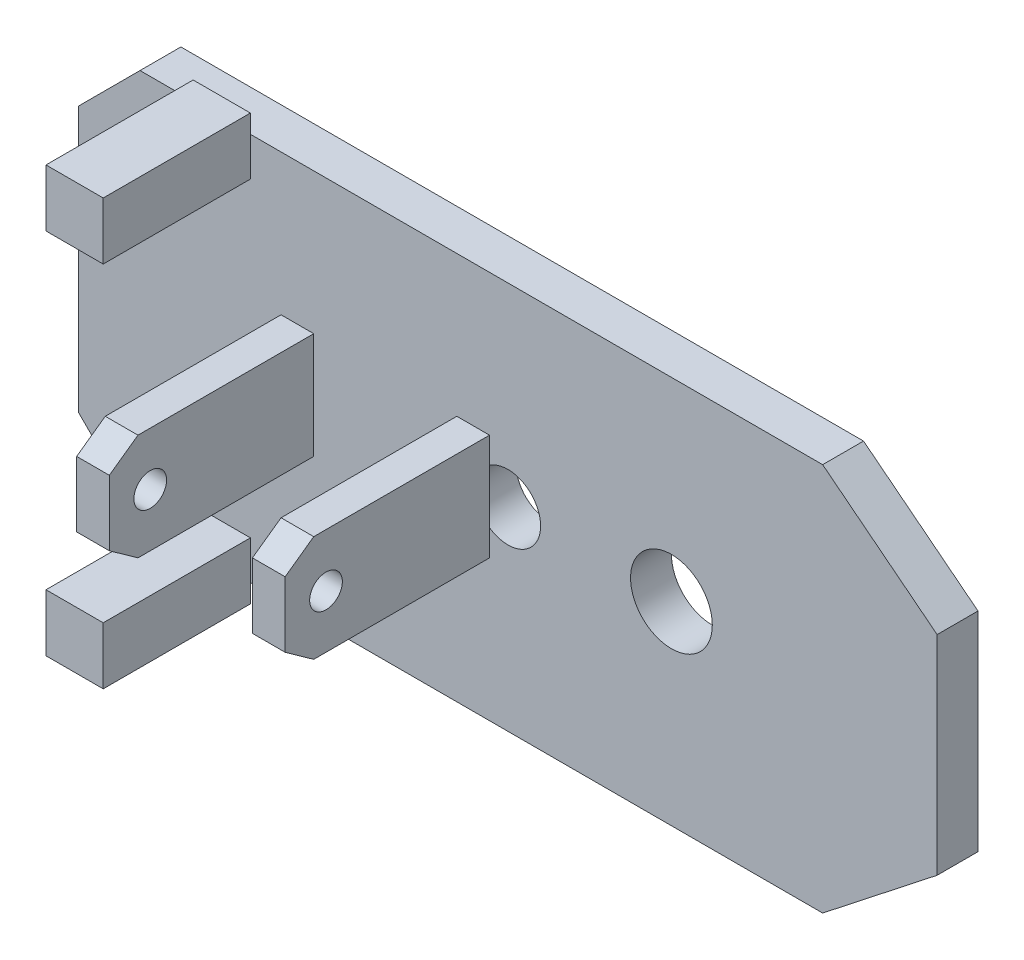
SolidWorks part; units mm, degrees
ref_plane "Front Plane" through (0, 0, 0) normal (0, 0, 1) x (1, 0, 0)
ref_plane "Top Plane" through (0, 0, 0) normal (0, 1, 0) x (1, 0, 0)
ref_plane "Right Plane" through (0, 0, 0) normal (1, 0, 0) x (0, 0, -1)
ref_plane "PL_Sole_Plate_base" through (0, 0, -50) normal (0, 0, 1) x (1, 0, 0)
sketch "SK_Sole_Plate" plane through (0, 0, -50) normal (0, 0, 1) x (1, 0, 0)
  line L0 (-60, -47.5) -> (107, -47.5)
  line L1 (107, -47.5) -> (135, -25.5)
  line L2 (135, -25.5) -> (135, 25.5)
  line L3 (135, 25.5) -> (107, 47.5)
  line L4 (107, 47.5) -> (-60, 47.5)
  line L5 (-60, 47.5) -> (-75, 32.5)
  line L6 (-75, 32.5) -> (-75, -32.5)
  line L7 (-75, -32.5) -> (-60, -47.5)
  circle A0 centre (70, 0) radius 10
  circle A1 centre (30, 0) radius 8
  dimension "D17_SK_Sole_Plate" = 20
  dimension "D19_SK_Sole_Plate" = 16
  dimension "P1" = 60
  dimension "P2" = 47.5
  dimension "P3" = 107
  dimension "P4" = 47.5
  dimension "P5" = 135
  dimension "P6" = 25.5
  dimension "P7" = 135
  dimension "P8" = 25.5
  dimension "P9" = 107
  dimension "P10" = 47.5
  dimension "P11" = 60
  dimension "P12" = 47.5
  dimension "P13" = 75
  dimension "P14" = 32.5
  dimension "P15" = 75
  dimension "P16" = 32.5
  dimension "P18" = 70
  dimension "P20" = 30
extrude "Sole_Plate" add sketch "SK_Sole_Plate" along normal blind 10
ref_plane "PL_Clevis_Front_base" through (17.5, 0, 0) normal (1, 0, 0) x (0, 0, -1)
sketch "SK_Clevis_Front" plane through (17.5, 0, 0) normal (1, 0, 0) x (0, 0, -1)
  line L0 (40, -13) -> (40, 13)
  line L1 (40, 13) -> (-3, 13)
  line L2 (-3, 13) -> (-10, 8)
  line L3 (-10, 8) -> (-10, -8)
  line L4 (-10, -8) -> (-3, -13)
  line L5 (-3, -13) -> (40, -13)
  circle A0 centre (0, 0) radius 4
  dimension "D13_SK_Clevis_Front" = 8
  dimension "P1" = 40
  dimension "P2" = 13
  dimension "P3" = 40
  dimension "P4" = 13
  dimension "P5" = 3
  dimension "P6" = 13
  dimension "P7" = 10
  dimension "P8" = 8
  dimension "P9" = 10
  dimension "P10" = 8
  dimension "P11" = 3
  dimension "P12" = 13
extrude "Clevis_Front" add sketch "SK_Clevis_Front" along normal blind 8
ref_plane "PL_Clevis_Back_base" through (-25.5, 0, 0) normal (1, 0, 0) x (0, 0, -1)
sketch "SK_Clevis_Back" plane through (-25.5, 0, 0) normal (1, 0, 0) x (0, 0, -1)
  line L0 (40, -13) -> (40, 13)
  line L1 (40, 13) -> (-3, 13)
  line L2 (-3, 13) -> (-10, 8)
  line L3 (-10, 8) -> (-10, -8)
  line L4 (-10, -8) -> (-3, -13)
  line L5 (-3, -13) -> (40, -13)
  circle A0 centre (0, 0) radius 4
  dimension "D13_SK_Clevis_Back" = 8
  dimension "P1" = 40
  dimension "P2" = 13
  dimension "P3" = 40
  dimension "P4" = 13
  dimension "P5" = 3
  dimension "P6" = 13
  dimension "P7" = 10
  dimension "P8" = 8
  dimension "P9" = 10
  dimension "P10" = 8
  dimension "P11" = 3
  dimension "P12" = 13
extrude "Clevis_Back" add sketch "SK_Clevis_Back" along normal blind 8
ref_plane "PL_Post_Lat_base" through (0, 0, -40) normal (0, 0, 1) x (1, 0, 0)
sketch "SK_Post_Lat" plane through (0, 0, -40) normal (0, 0, 1) x (1, 0, 0)
  line L0 (-47, 38) -> (-33, 38)
  line L1 (-33, 38) -> (-33, 52)
  line L2 (-33, 52) -> (-47, 52)
  line L3 (-47, 52) -> (-47, 38)
  dimension "P1" = 47
  dimension "P2" = 38
  dimension "P3" = 33
  dimension "P4" = 38
  dimension "P5" = 33
  dimension "P6" = 52
  dimension "P7" = 47
  dimension "P8" = 52
extrude "Post_Lat" add sketch "SK_Post_Lat" along normal blind 36
ref_plane "PL_Post_Med_base" through (0, 0, -40) normal (0, 0, 1) x (1, 0, 0)
sketch "SK_Post_Med" plane through (0, 0, -40) normal (0, 0, 1) x (1, 0, 0)
  line L0 (-47, -52) -> (-33, -52)
  line L1 (-33, -52) -> (-33, -38)
  line L2 (-33, -38) -> (-47, -38)
  line L3 (-47, -38) -> (-47, -52)
  dimension "P1" = 47
  dimension "P2" = 52
  dimension "P3" = 33
  dimension "P4" = 52
  dimension "P5" = 33
  dimension "P6" = 38
  dimension "P7" = 47
  dimension "P8" = 38
extrude "Post_Med" add sketch "SK_Post_Med" along normal blind 36
ref_axis "AX_Roll" through (-85.5, 0, 0) along (1, 0, 0)
sketch "SK_RodBalls" plane through (0, 0, 0) normal (0, 0, 1) x (1, 0, 0)
  point P0 (-40, 45)
  point P2 (-40, -45)
  dimension "P1" = 40
  dimension "P2" = 45
  dimension "P3" = 40
  dimension "P4" = 45
equation "\"Foot_length\" = 210"
equation "\"Foot_width\" = 95"
equation "\"Ankle_height\" = 50"
